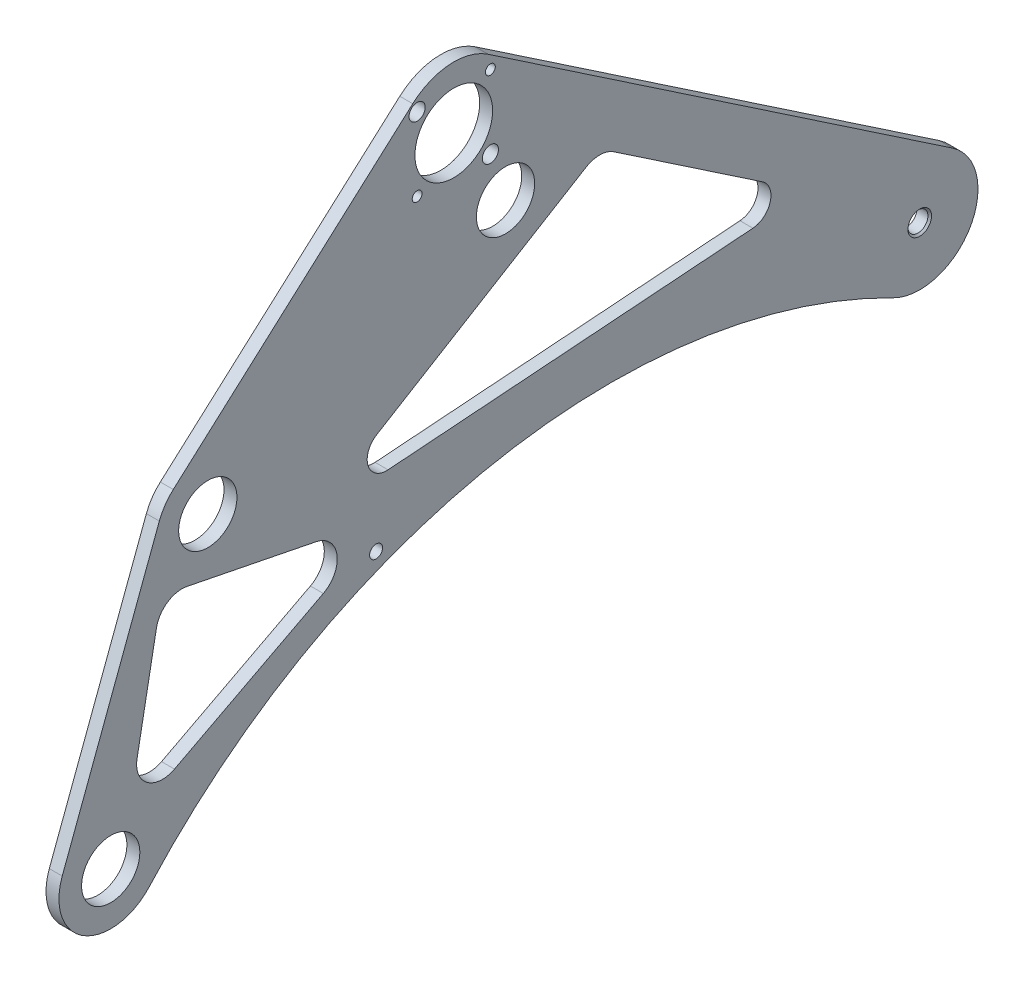
SolidWorks part; units mm, degrees
material "Acrylic (Medium-high impact)"
ref_plane "Front Plane" through (0, 0, 0) normal (0, 0, 1) x (1, 0, 0)
ref_plane "Top Plane" through (0, 0, 0) normal (0, 1, 0) x (1, 0, 0)
ref_plane "Right Plane" through (0, 0, 0) normal (1, 0, 0) x (0, 0, -1)
sketch "Sketch1" plane through (0, 0, 0) normal (1, 0, 0) x (0, 0, -1)
  line L0 (-548.7618, -304.8) -> (152.435, -304.8)
  line L1 (-192.8252, -101.6) -> (-152.4, -101.6)
  line L2 (-234.95, -143.7248) -> (-234.95, -186.4752)
  line L3 (-192.8252, -228.6) -> (-152.4, -228.6)
  line L4 (-152.4, -101.6) -> (-152.4, -228.6)
  line L5 (-211.5668, 162.8819) -> (-186.1668, 121.6069)
  line L6 (-189.2955, 96.7492) -> (-382.9705, -90.5758)
  line L7 (-415.6016, -69.1775) -> (-367.9766, 57.8225)
  line L8 (-352.0597, 70.6017) -> (-289.9638, 79.4126)
  line L9 (-285.1603, 82.8921) -> (-246.539, 161.2427)
  circle A1 centre (0, 0) radius 6.35
  circle A6 centre (-396.875, -76.2) radius 9.525
  circle A7 centre (-349.25, 50.8) radius 9.525
  circle A8 centre (-203.2, 111.125) radius 9.525
  arc A9 (-234.95, -186.4752) -> (-192.8252, -228.6) centre (-192.8252, -186.4752) ccw
  arc A10 (-192.8252, -101.6) -> (-234.95, -143.7248) centre (-192.8252, -143.7248) ccw
  circle A11 centre (-230.9942, 0) radius 120.65
  circle A12 centre (-228.6, 152.4) radius 29.845
  arc A18 (-246.539, 161.2427) -> (-211.5668, 162.8819) centre (-228.6, 152.4) cw
  arc A19 (-186.1668, 121.6069) -> (-189.2955, 96.7492) centre (-203.2, 111.125) cw
  arc A20 (-382.9705, -90.5758) -> (-415.6016, -69.1775) centre (-396.875, -76.2) cw
  arc A21 (-367.9766, 57.8225) -> (-352.0597, 70.6017) centre (-349.25, 50.8) cw
  arc A22 (-289.9638, 79.4126) -> (-285.1603, 82.8921) centre (-290.8559, 85.6997) ccw
  point P18 (-285.7931, 74.8706)
  point P22 (0, 0)
  circle B0 centre (-349.25, 50.8) radius 20
  line B1 (-396.875, -76.2) -> (-382.9261, -60.8997)
  circle B2 centre (-396.875, -76.2) radius 20
  circle B3 centre (-203.2, 111.125) radius 20
  line B4 (-228.6, 152.4) -> (-225.2662, 168.6097)
  circle B5 centre (-228.6, 152.4) radius 20
  circle B6 centre (-290.8559, 85.6997) radius 6.35
  dimension "D1" = 12.7
  dimension "D2" = 19.05
  dimension "D3" = 42.1248
  dimension "D4" = 127
  dimension "D7" = 203.2
  dimension "D6" = 241.3
  dimension "D16" = 59.69
  dimension "D5" = 82.55
  dimension "D8" = 304.8
  dimension "D9" = 152.4
  dimension "D10" = 396.875
  dimension "D11" = 76.2
  dimension "D12" = 349.25
  dimension "D13" = 50.8
  dimension "D14" = 203.2
  dimension "D15" = 111.125
  dimension "D17" = 228.6
  dimension "D18" = 152.4
sketch_block_instance "Block1-1"
sketch_block "Block1" parameters "D1"=8
sketch_block_instance "Block2-1"
sketch_block "Block2" parameters "D1"=8
sketch_block_instance "Block3-1"
sketch_block "Block3" parameters "D1"=8
sketch_block_instance "Block4-1"
sketch_block "Block4" parameters "D1"=40, "D2"=8
sketch_block_instance "Block5-1"
sketch_block "Block5" parameters "D1"=8
other "Belt1"
sketch "Sketch2" plane through (0, 0, 0) normal (1, 0, 0) x (0, 0, -1)
  line L1 (-420.6578, -67.2815) -> (-373.0328, 59.7185)
  line L3 (-366.1902, 69.7259) -> (-248.7165, 174.8745)
  line L5 (-211.7241, 177.3996) -> (15.9877, 23.6839)
  line L6 (-1001.8623, -101.6) -> (216.545, -101.6) construction
  line L7 (-1029.8132, 182.5625) -> (188.5941, 182.5625) construction
  arc A0 (-366.1902, 69.7259) -> (-373.0328, 59.7185) centre (-349.25, 50.8) ccw
  arc A2 (-420.6578, -67.2815) -> (-377.9906, -93.1865) centre (-396.875, -76.2) ccw
  arc A4 (-211.7241, 177.3996) -> (-248.7165, 174.8745) centre (-228.6, 152.4) ccw
  arc A5 (-12.9753, -25.4592) -> (15.9877, 23.6839) centre (0, 0) ccw
  arc A8 (-377.9906, -93.1865) -> (-12.9753, -25.4592) centre (-151.3783, -297.0244) cw
  circle A12 centre (-396.875, -76.2) radius 9.525 construction
  circle A13 centre (-349.25, 50.8) radius 9.525 construction
  dimension "D1" = 25.4
  dimension "D2" = 57.15
  dimension "D3" = 60.325
  dimension "D4" = 304.8
  dimension "D6" = 284.1625
extrude "Boss-Extrude1" add sketch "Sketch2" along normal blind 6.35
sketch "Sketch3" plane through (6.35, 0, 0) normal (1, 0, 0) x (0, 0, -1)
  line L0 (-210.6395, 170.3605) -> (-246.5605, 134.4395) construction
  line L1 (-228.6, 152.4) -> (-228.6, 205.0182) construction
  line L2 (-246.5605, 170.3605) -> (-210.6395, 134.4395) construction
  circle A0 centre (-203.2, 111.125) radius 14.2875
  circle A1 centre (-349.25, 50.8) radius 14.2875
  circle A2 centre (-396.875, -76.2) radius 14.2875
  circle A3 centre (-228.6, 152.4) radius 19.05
  circle A5 centre (-246.5605, 134.4395) radius 2.413
  circle A7 centre (-210.6395, 134.4395) radius 3.9687
  circle A8 centre (-210.6395, 170.3605) radius 2.413
  circle A9 centre (-246.5605, 170.3605) radius 3.9687
  point P18 (-228.6, 152.4)
  point P28 (-228.6, 152.4)
  dimension "D1" = 38.1
  dimension "D2" = 28.575
  dimension "D3" = 4.826
  dimension "D4" = 50.8
  dimension "D5" = 45
  dimension "D6" = 7.9375
  dimension "D7" = 50.8
extrude "Cut-Extrude1" cut sketch "Sketch3" against normal up to next
hole_wizard "3/8 Clearance Hole2" positions "Sketch7" profile "Sketch8" hole size "3/8" standard "ANSI Inch" end condition through all
sketch "Sketch7" plane through (6.35, 0, 0) normal (1, 0, 0) x (0, 0, -1)
  point P0 (0, 0)
sketch "Sketch8" plane through (6.35, 0, 0) normal (0, 1, 0) x (0, 0, -1)
  line L0 (0, 0) -> (0, 6.35)
  line L1 (0, 6.35) -> (4.9022, 6.35)
  line L2 (4.9022, 6.35) -> (4.9022, 0.8915)
  line L3 (4.9022, 0.8915) -> (5.7937, 0)
  line L5 (5.7937, 0) -> (0, 0)
  line L6 (-4.9022, 0.8915) -> (-5.7937, 0) construction
  line L11 (0, -6.35) -> (0, 107.95) construction
  dimension "Thru Hole Dia." = 9.8044
  dimension "Thru Hole Depth" = 6.35
  dimension "Near C'Sink Dia." = 11.5875
  dimension "Near C'Sink Angle" = 90
sketch "Sketch9" plane through (6.35, 0, 0) normal (1, 0, 0) x (0, 0, -1)
  line L0 (-495.9857, -101.6) -> (27.4607, -101.6) construction
  line L1 (100.4878, 182.5625) -> (-422.9585, 182.5625) construction
  arc A0 (-211.7241, 177.3996) -> (-248.7165, 174.8745) centre (-228.6, 152.4) ccw construction
  arc A1 (-420.6578, -67.2815) -> (-377.9906, -93.1865) centre (-396.875, -76.2) ccw construction
  dimension "D1" = 284.1625
hole_wizard "1/4 (0.2500) Dowel Hole2" positions "Sketch12" profile "Sketch13" hole size "1/4" standard "ANSI Inch" end condition through all
sketch "Sketch12" plane through (6.35, 0, 0) normal (1, 0, 0) x (0, 0, -1)
  point P0 (-266.7, -6.35)
  dimension "D1" = 266.7
sketch "Sketch13" plane through (6.35, -6.35, 266.7) normal (0, 1, 0) x (0, 0, -1)
  line L0 (0, 0) -> (0, 6.35)
  line L1 (0, 6.35) -> (3.175, 6.35)
  line L2 (3.175, 6.35) -> (3.175, 0)
  line L5 (3.175, 0) -> (0, 0)
  line L11 (0, -6.35) -> (0, 107.95) construction
  dimension "Thru Hole Dia." = 6.35
  dimension "Thru Hole Depth" = 6.35
sketch "Sketch14" plane through (6.35, 0, 0) normal (1, 0, 0) x (0, 0, -1)
  line L0 (-365.6004, -49.3596) -> (-292.5754, -11.2596)
  line L1 (-295.9593, 12.4534) -> (-359.4593, 25.1534)
  line L2 (-374.4325, 15.0405) -> (-383.9575, -35.7595)
  line L3 (-77.2075, 55.9493) -> (-149.9685, 105.0662)
  line L4 (-163.6599, 105.3991) -> (-266.4749, 43.0436)
  line L6 (-260.8375, 25.4) -> (-81.8386, 38.5553)
  line L9 (15.9877, 23.6839) -> (-211.7241, 177.3996) construction
  arc A0 (-383.9575, -35.7595) -> (-365.6004, -49.3596) centre (-371.475, -38.1) ccw
  arc A1 (-292.5754, -11.2596) -> (-295.9593, 12.4534) centre (-298.45, 0) ccw
  arc A2 (-359.4593, 25.1534) -> (-374.4325, 15.0405) centre (-361.95, 12.7) ccw
  circle A3 centre (-396.875, -76.2) radius 14.2875 construction
  circle A4 centre (-349.25, 50.8) radius 14.2875 construction
  circle A5 centre (-266.7, -6.35) radius 3.175 construction
  arc A9 (-149.9685, 105.0662) -> (-163.6599, 105.3991) centre (-157.0742, 94.5401) ccw
  arc A13 (-260.8375, 25.4) -> (-266.4749, 43.0436) centre (-261.5356, 34.8994) cw
  circle A15 centre (-203.2, 111.125) radius 14.2875 construction
  arc A21 (-81.8386, 38.5553) -> (-77.2075, 55.9493) centre (-82.5367, 48.0546) ccw
  point P21 (0, 0)
  point P44 (-288.2635, 17.3613)
  dimension "D1" = 38.1
  dimension "D2" = 25.4
  dimension "D3" = 25.4
  dimension "D4" = 38.1
  dimension "D5" = 12.7
  dimension "D6" = 31.75
  dimension "D7" = 6.35
  dimension "D8" = 25.4
  dimension "D9" = 25.4
  dimension "D12" = 9.525
  dimension "D13" = 25.4
  dimension "D14" = 12.7
  dimension "D15" = 44.45
  dimension "D16" = 50.8
  dimension "D11" = 9.525
  dimension "D10" = 25.4
extrude "Cut-Extrude2" cut sketch "Sketch14" against normal through all
